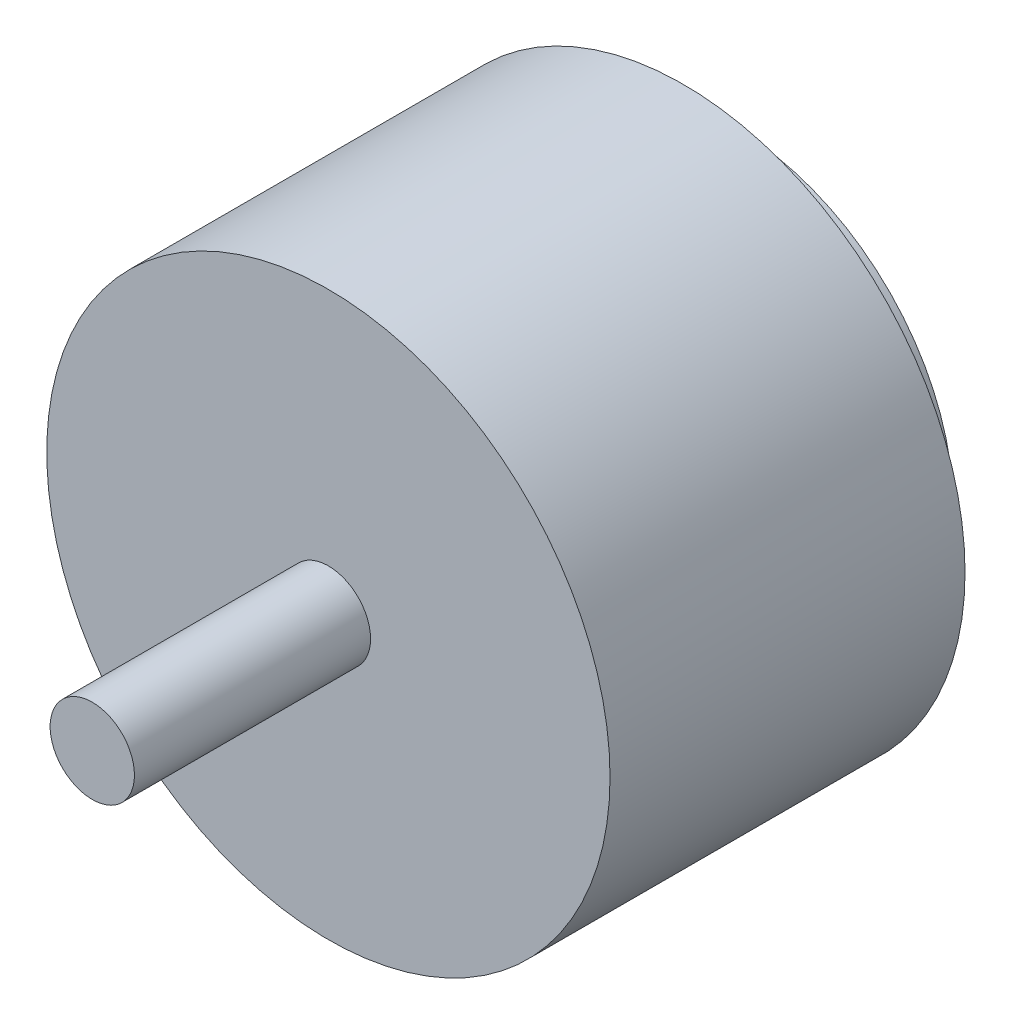
SolidWorks part; units mm, degrees
ref_plane "前视基准面" through (0, 0, 0) normal (0, 0, 1) x (1, 0, 0)
ref_plane "上视基准面" through (0, 0, 0) normal (0, 1, 0) x (1, 0, 0)
ref_plane "右视基准面" through (0, 0, 0) normal (1, 0, 0) x (0, 0, -1)
other "Configuration Table"
sketch "草图1" plane through (0, 0, 0) normal (0, 0, 1) x (1, 0, 0)
  circle A5 centre (0, 0) radius 13
  circle A6 centre (-9.5, 0) radius 1.6
  circle A7 centre (0, -9.5) radius 1.6
  circle A8 centre (9.5, 0) radius 1.6
  circle A9 centre (0, 9.5) radius 1.6
extrude "电机底座" add sketch "草图1" along normal blind 3
sketch "草图2" plane through (0, 0, 0) normal (0, 0, 1) x (1, 0, 0)
  circle A1 centre (0, 0) radius 16.7
extrude "电机转子包络" add sketch "草图2" along normal blind 21.05 from offset 3
sketch "草图3" plane through (0, 0, 0) normal (0, 0, 1) x (1, 0, 0)
  circle A0 centre (0, 0) radius 2.5
extrude "M5桨轴_外伸14mm" add sketch "草图3" along normal blind 14 from offset 24.05
ref_axis "电机输出轴_Z" through (0, 0, -1.9025) along (0, 0, 1)
